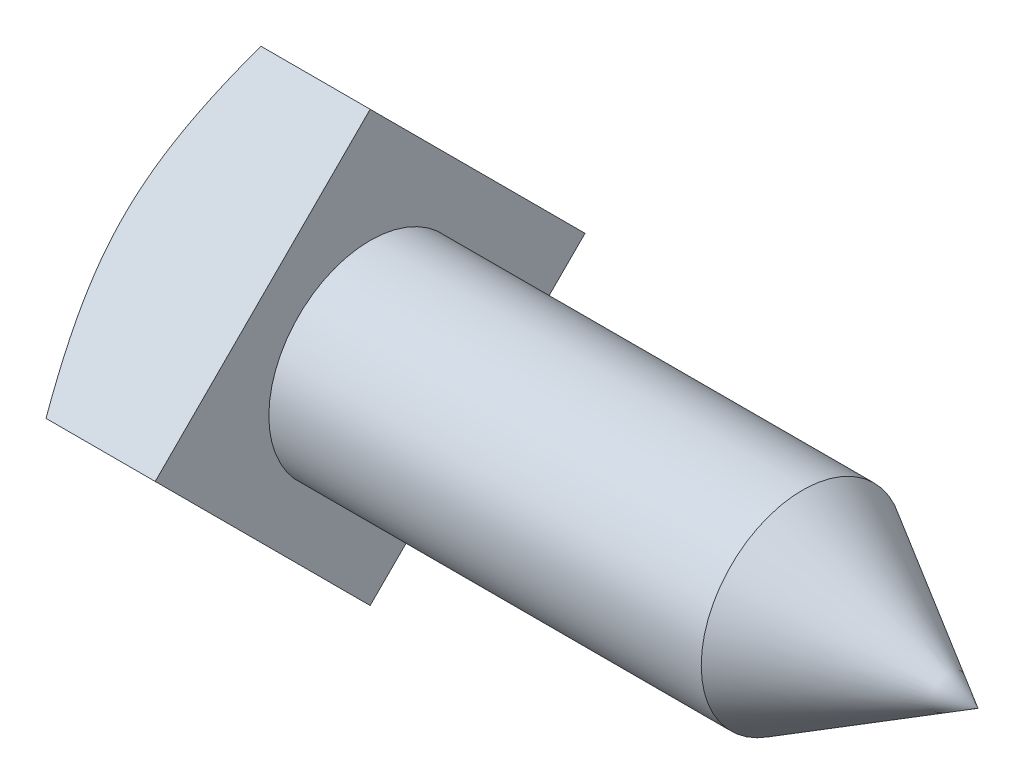
SolidWorks part; units mm, degrees
extrude "BaseHead" add sketch "Sketch1" along normal blind 17.3736
sketch "Sketch1" plane through (0, 0, 0) normal (1, 0, 0) x (0, 0.7071, -0.7071)
  line L0 (19.05, -19.05) -> (-19.05, -19.05)
  line L1 (19.05, -19.05) -> (19.05, 19.05)
  line L2 (-19.05, 19.05) -> (19.05, 19.05)
  line L3 (-19.05, 19.05) -> (-19.05, -19.05)
  dimension "Width_flats" = 38.1
  dimension "D1" = 19.05
  dimension "D2" = 38.1
  dimension "D3" = 19.05
ref_plane "Plane1" through (0, 0, 0) normal (0, 0, 1) x (1, 0, 0)
ref_plane "Plane2" through (0, 0, 0) normal (0, 1, 0) x (1, 0, 0)
ref_plane "Plane3" through (0, 0, 0) normal (1, 0, 0) x (0, 0, -1)
sketch "Sketch2" plane through (0, 0, 0) normal (0, 0, 1) x (1, 0, 0)
  line L0 (17.3736, 0) -> (17.3736, 12.7)
  line L1 (17.3736, 12.7) -> (71.5766, 12.7)
  line L2 (71.5766, 12.7) -> (93.5736, 0)
  line L3 (71.5766, -12.7) -> (93.5736, 0) construction
  line L4 (93.5736, 0) -> (17.3736, 0)
  line L5 (17.3736, 0) -> (17.3736, 26.9408) construction
  line L6 (0, 0) -> (107.95, 0) construction
  line L7 (17.3736, -12.7) -> (71.5766, -12.7) construction
  dimension "Length" = 76.2
  dimension "Diameter" = 25.4
  dimension "Point_ang" = 60
revolve "Body" add sketch "Sketch2" angle 360 about L6
sketch "Sketch3" plane through (0, 0, 0) normal (0, 0, 1) x (1, 0, 0)
  line L0 (0, 19.05) -> (-12.7, 19.05)
  line L1 (0, 0) -> (0, 26.9408) construction
  line L2 (0, 19.05) -> (15.5237, 52.3408)
  line L3 (15.5237, 52.3408) -> (-12.7, 52.3408)
  line L4 (-12.7, 52.3408) -> (-12.7, 19.05)
  line L5 (0, 0) -> (31.75, 0) construction
  line L6 (17.3736, 26.9408) -> (0, 26.9408) construction
  dimension "D1" = 19.05
  dimension "D2" = 25.4
  dimension "D4" = 12.7
revolve "HeadChamfer" cut sketch "Sketch3" angle 360 about L5
fillet "HeadFillet" [suppressed]
equation "\"D1@Sketch1\" = \"Width_flats@Sketch1\" / 2"
equation "\"D2@Sketch1\" = \"Width_flats@Sketch1\""
equation "\"D3@Sketch1\" = \"D1@Sketch1\""
equation "\"D1@Sketch3\" = \"Width_flats@Sketch1\" / 2"
